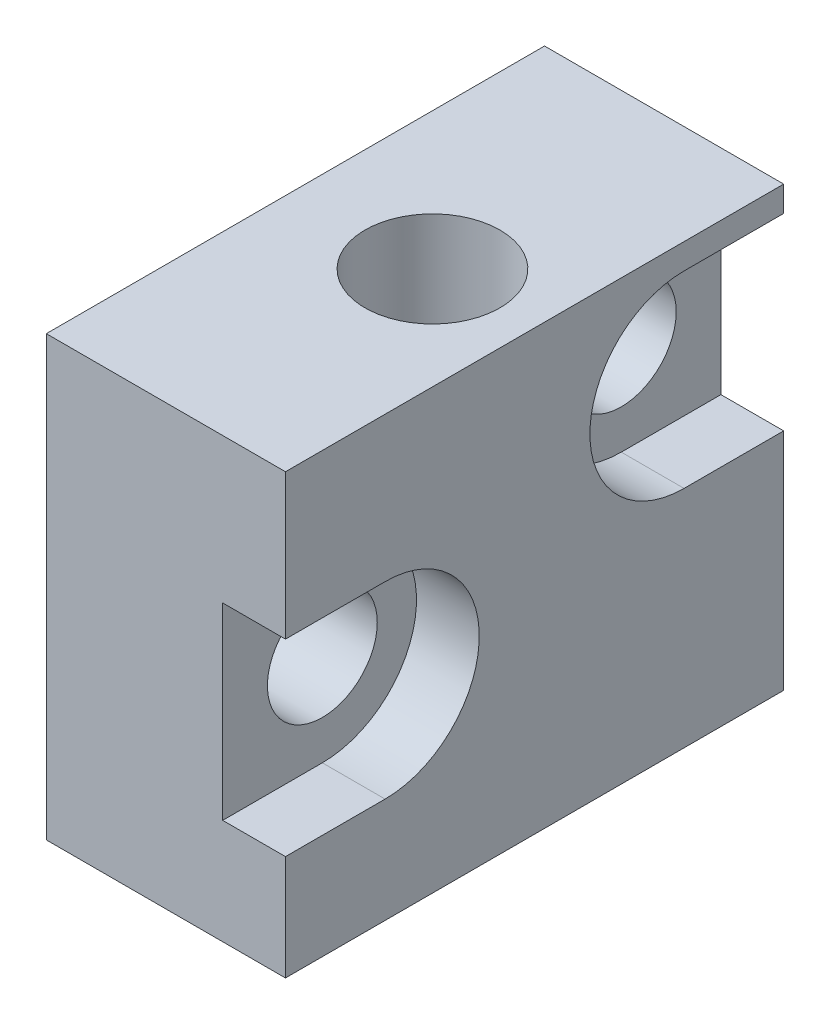
SolidWorks part; units mm, degrees
other "Markup1"
sketch "Sketch9"
material "PET"
ref_plane "Front Plane" through (0, 0, 0) normal (1, 0, 0) x (0, 1, 0)
ref_plane "Top Plane" through (0, 0, 0) normal (0, 0, 1) x (0, 1, 0)
ref_plane "Right Plane" through (0, 0, 0) normal (0, 1, 0) x (-1, 0, 0)
sketch "Sketch1" plane through (0, 0, 0) normal (1, 0, 0) x (0, 1, 0)
  line L1 (5.715, -7.9375) -> (-5.715, -7.9375)
  line L2 (5.715, -7.9375) -> (5.715, 7.9375)
  line L3 (5.715, 7.9375) -> (-5.715, 7.9375)
  line L4 (-5.715, -7.9375) -> (-5.715, 7.9375)
  line L5 (5.715, -7.9375) -> (-5.715, 7.9375) construction
  line L6 (5.715, 7.9375) -> (-5.715, -7.9375) construction
  point P0 (0, 0)
  dimension "D1" = 15.875
  dimension "D2" = 11.43
extrude "Boss-Extrude1" add sketch "Sketch1" along normal blind 7.62
sketch "Sketch3" plane through (0, -5.715, 0) normal (0, -1, 0) x (1, 0, 0)
  line L10 (0, 7.9375) -> (0, -7.9375)
  line L11 (0, -7.9375) -> (7.62, -7.9375)
  line L12 (7.62, -7.9375) -> (7.62, 7.9375)
  line L13 (7.62, 7.9375) -> (0, 7.9375)
  line L14 (0, 7.9375) -> (0, -7.9375)
  line L15 (0, -7.9375) -> (7.62, -7.9375)
  line L16 (7.62, -7.9375) -> (7.62, 7.9375)
  line L17 (7.62, 7.9375) -> (0, 7.9375)
  circle A0 centre (4.3663, 0) radius 2.15
  circle A1 centre (4.3663, 0) radius 5 construction
  circle A2 centre (4.3663, 0) radius 3 construction
  point P2 (9.3663, 0)
  point P3 (2.2163, 0)
  point P6 (-6.35, 0)
  dimension "D1" = 4.3
  dimension "D2" = 10
  dimension "D6" = 6
  dimension "D3" = 15.7163
  dimension "D4" = 6.35
  dimension "D5" = 0
extrude "Cut-Extrude1" cut sketch "Sketch3" against normal blind 22.2885 contours A0 region at (4.3663, -5.715, 0)
sketch "Sketch4" plane through (7.62, 0, 0) normal (1, 0, 0) x (0, 1, 0)
  line L0 (-5.715, 7.9375) -> (-5.715, -7.9375) construction
  line L1 (1.905, -4.7625) -> (-1.905, -4.7625) construction
  line L2 (1.905, -4.7625) -> (1.905, 4.7625) construction
  line L3 (1.905, 4.7625) -> (-1.905, 4.7625) construction
  line L4 (-1.905, -4.7625) -> (-1.905, 4.7625) construction
  line L5 (1.905, -4.7625) -> (-1.905, 4.7625) construction
  line L6 (1.905, 4.7625) -> (-1.905, -4.7625) construction
  line L7 (5.715, 7.9375) -> (-5.715, 7.9375) construction
  circle A5 centre (-1.905, 4.7625) radius 1.75
  circle A6 centre (1.905, -4.7625) radius 1.75
  point P0 (0, 0)
  dimension "D3" = 3.5
  dimension "D1" = 3.81
  dimension "D2" = 3.175
extrude "Cut-Extrude2" cut sketch "Sketch4" against normal blind 22.2885 contours A5 | A6 region at (7.62, -1.905, 4.7625) region at (7.62, 1.905, -4.7625)
sketch "Sketch5" plane through (7.62, 0, 0) normal (1, 0, 0) x (0, 1, 0)
  line L0 (-4.905, 4.7625) -> (-4.905, 7.9375)
  line L1 (5.715, 7.9375) -> (-5.715, 7.9375) construction
  line L2 (-4.905, 7.9375) -> (1.095, 7.9375)
  line L3 (1.095, 7.9375) -> (1.095, 4.7625)
  line L4 (4.905, -4.7625) -> (4.905, -7.9375)
  line L5 (-5.715, -7.9375) -> (5.715, -7.9375) construction
  line L6 (4.905, -7.9375) -> (-1.095, -7.9375)
  line L7 (-1.095, -7.9375) -> (-1.095, -4.7625)
  line L8 (-1.905, 1.7625) -> (-5.715, 1.7625)
  line L9 (-5.715, 7.9375) -> (-5.715, -7.9375) construction
  circle A0 centre (1.905, -4.7625) radius 1.75 construction
  circle A1 centre (-1.905, 4.7625) radius 1.75 construction
  circle A2 centre (1.905, -4.7625) radius 1.75 construction
  circle A3 centre (-1.905, 4.7625) radius 1.75 construction
  circle A4 centre (-1.905, 4.7625) radius 3
  circle A5 centre (1.905, -4.7625) radius 3
  circle M3 centre (-1.905, 4.7625) radius 1.75
  circle M4 centre (1.905, -4.7625) radius 1.75
  line M6 (-5.715, -7.9375) -> (5.715, -7.9375)
  line M8 (5.715, 7.9375) -> (-5.715, 7.9375)
  dimension "D1" = 6
extrude "Cut-Extrude3" cut sketch "Sketch5" against normal blind 2 contours A4 M3 | A4 L3 L0 M8 | A5 M4 | A5 L7 L4 M6 region at (7.62, -4.8371, 6.35) region at (7.62, -1.905, 7.6776) region at (7.62, 1.905, -7.6776) region at (7.62, 4.8371, -6.35)
sketch "Sketch6" plane through (7.62, 0, 0) normal (1, 0, 0) x (0, 1, 0)
  line L0 (-5.715, -7.9375) -> (-1.095, -7.9375) construction
  line L1 (-5.715, 7.9375) -> (-8.255, 7.9375)
  line L2 (-5.715, 7.9375) -> (-5.715, -7.9375)
  line L3 (-5.715, -7.9375) -> (-8.255, -7.9375)
  line L4 (-8.255, 7.9375) -> (-8.255, -7.9375)
  dimension "D1" = 2.54
extrude "Boss-Extrude2" add sketch "Sketch6" against normal up to vertex (7.62 mm away) up to point (0, -5.715, 7.9375)
sketch "Sketch8" plane through (0, 5.715, 0) normal (0, 1, 0) x (-1, 0, 0)
  circle A0 centre (-4.3663, 0) radius 2.15 construction
  circle A1 centre (-4.3663, 0) radius 2.15
extrude "Cut-Extrude4" cut sketch "Sketch8" against normal blind 18.796
